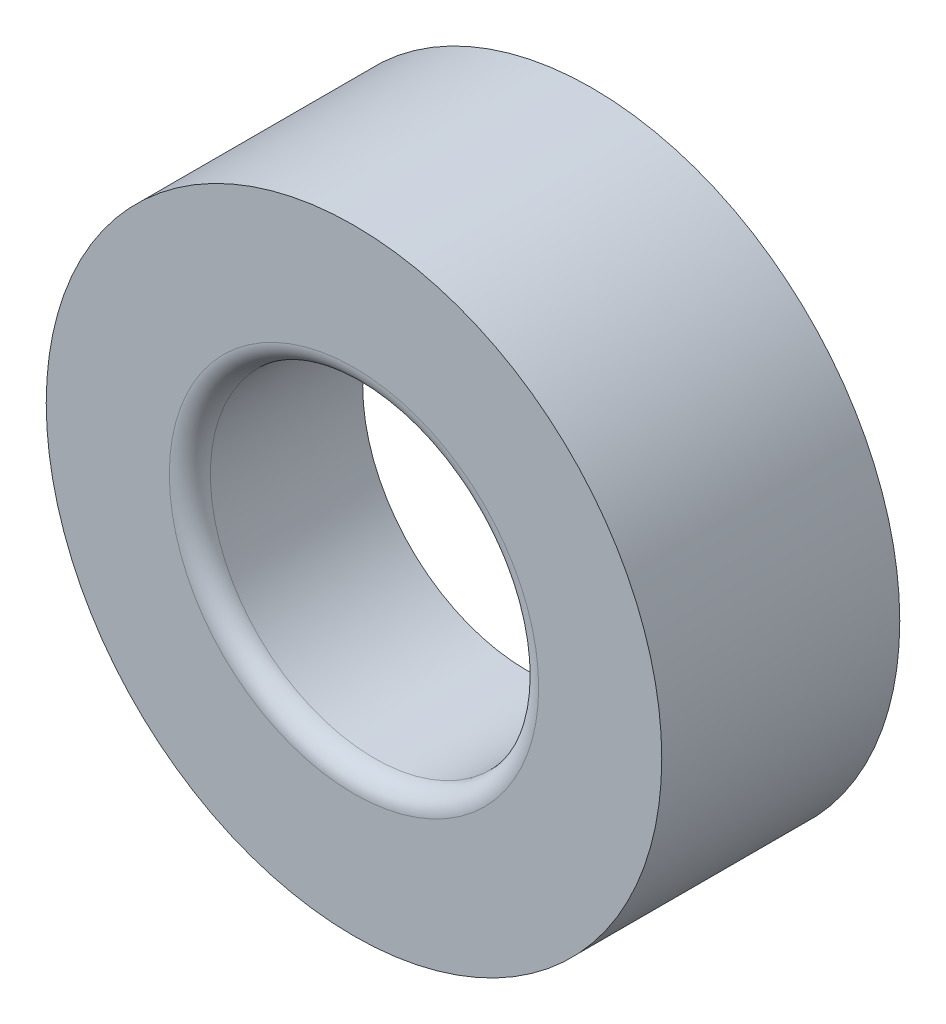
SolidWorks part; units mm, degrees
ref_plane "Front Plane" through (0, 0, 0) normal (0, 0, 1) x (1, 0, 0)
ref_plane "Top Plane" through (0, 0, 0) normal (0, 1, 0) x (1, 0, 0)
ref_plane "Right Plane" through (0, 0, 0) normal (1, 0, 0) x (0, 0, -1)
sketch "Sketch1" plane through (0, 0, 0) normal (0, 0, 1) x (1, 0, 0)
  circle A0 centre (85.2065, -1.764) radius 7.5
  dimension "D1" = 15
extrude "Boss-Extrude1" add sketch "Sketch1" along normal blind 5.8
sketch "Sketch2" plane through (0, 0, 5.8) normal (0, 0, 1) x (1, 0, 0)
  circle A0 centre (85.2065, -1.764) radius 4
  dimension "D1" = 8
extrude "Cut-Extrude1" cut sketch "Sketch2" against normal through all
sketch "Sketch3" plane through (0, 0, 0) normal (0, 0, -1) x (-1, 0, 0)
  circle A0 centre (-85.2065, -1.764) radius 6.3
  dimension "D1" = 12.6
extrude "Cut-Extrude2" cut sketch "Sketch3" against normal blind 1.5875
fillet "Fillet1" radius 0.5 1 edges at (89.2065, -1.764, 5.8)
